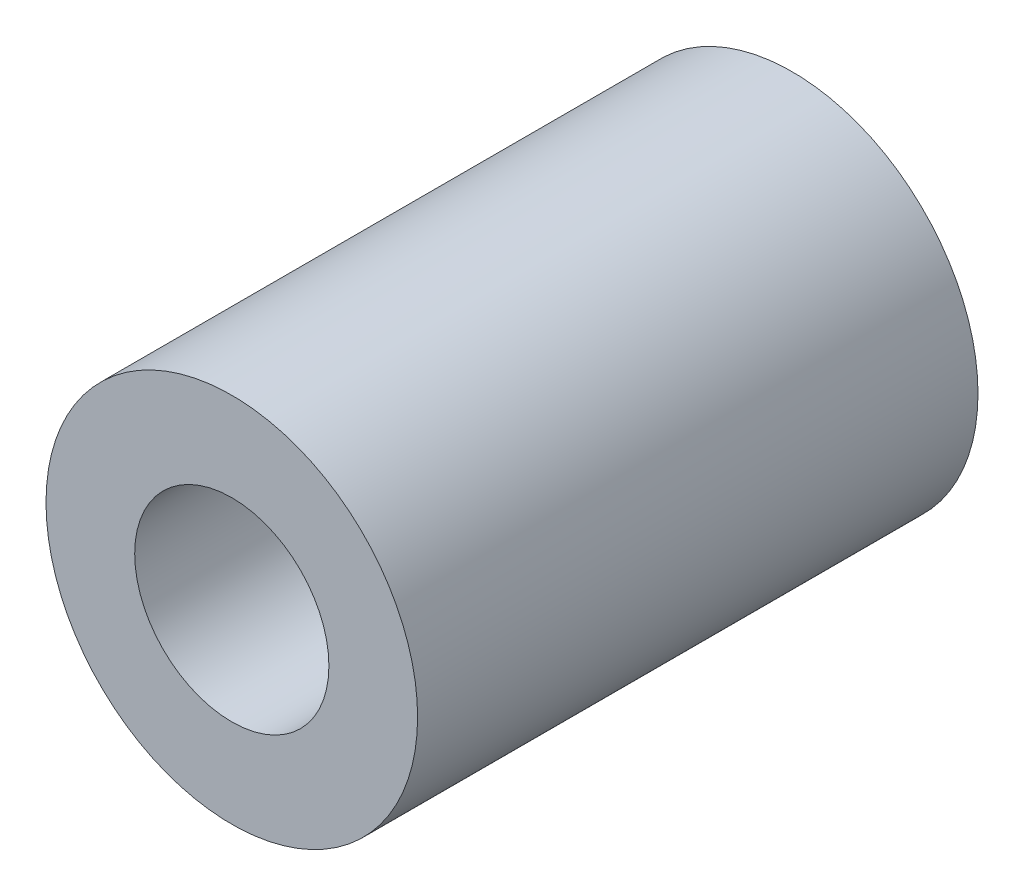
SolidWorks part; units mm, degrees
ref_plane "Front Plane" through (0, 0, 0) normal (0, 0, 1) x (1, 0, 0)
ref_plane "Top Plane" through (0, 0, 0) normal (0, 1, 0) x (1, 0, 0)
ref_plane "Right Plane" through (0, 0, 0) normal (1, 0, 0) x (0, 0, -1)
sketch "Sketch1" plane through (0, 0, 0) normal (0, 0, 1) x (1, 0, 0)
  circle A0 centre (0, 0) radius 2.4892
  circle A1 centre (0, 0) radius 4.7625
  dimension "D1" = 4.9784
  dimension "D2" = 9.525
extrude "Boss-Extrude1" add sketch "Sketch1" along normal mid plane 14.3637
